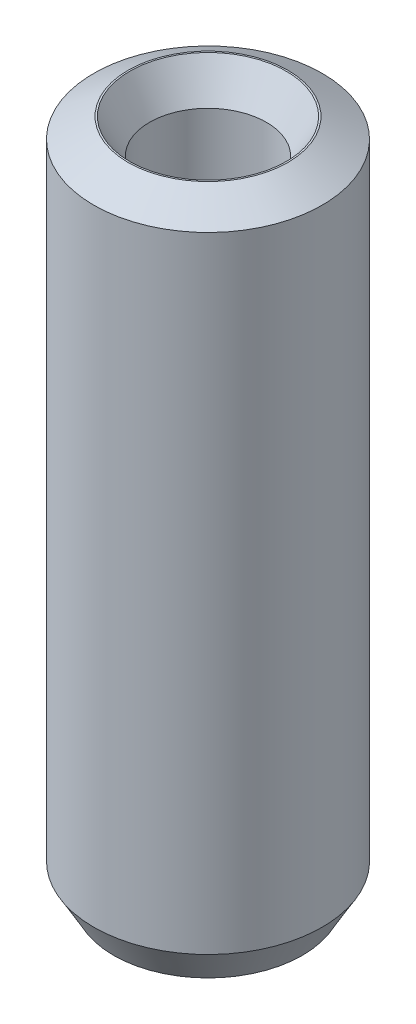
SolidWorks part; units mm, degrees
ref_plane "Front Plane" through (0, 0, 0) normal (0, 0, 1) x (1, 0, 0)
ref_plane "Top Plane" through (0, 0, 0) normal (0, 1, 0) x (1, 0, 0)
ref_plane "Right Plane" through (0, 0, 0) normal (1, 0, 0) x (0, 0, -1)
sketch "Sketch1" plane through (0, 0, 0) normal (0, 1, 0) x (1, 0, 0)
  circle A0 centre (0, 0) radius 15
  dimension "SLEEVE_OD" = 30
extrude "Boss-Extrude1" add sketch "Sketch1" along normal blind 89.2216
sketch "Sketch2" plane through (0, 0, 0) normal (0, 1, 0) x (1, 0, 0)
  circle A0 centre (0, 0) radius 7.6747
  dimension "BORE_D" = 15.3493
extrude "Cut-Extrude1" cut sketch "Sketch2" along normal through all
chamfer "Chamfer1" distance 2.6026 angle 60 4 edges at (0, 89.2216, 7.6747) (0, 0, 7.6747) (0, 0, 15) (0, 89.2216, 15) first distance on face at (0, 89.2216, 7.6747) first distance on face at (0, 0, 7.6747) first distance on face at (0, 89.2216, 15)
